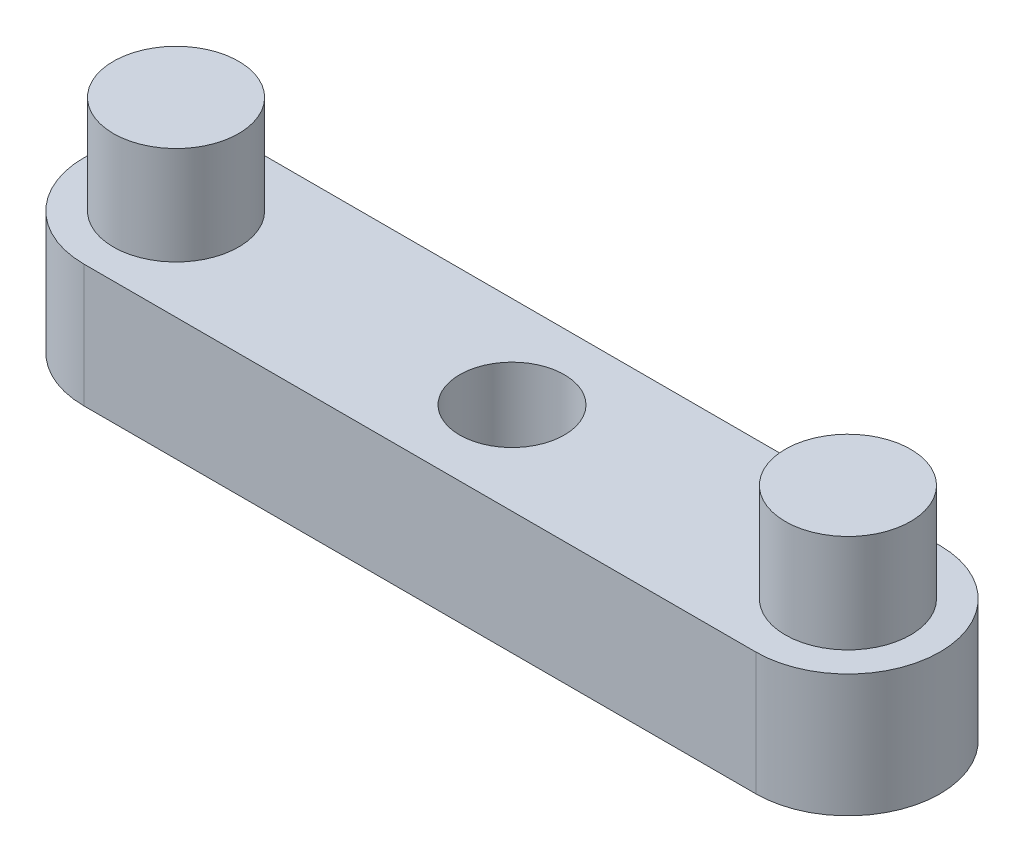
SolidWorks part; units mm, degrees
ref_plane "Front Plane" through (0, 0, 0) normal (0, 0, 1) x (1, 0, 0)
ref_plane "Top Plane" through (0, 0, 0) normal (0, 1, 0) x (1, 0, 0)
ref_plane "Right Plane" through (0, 0, 0) normal (1, 0, 0) x (0, 0, -1)
sketch "Sketch1" plane through (0, 0, 0) normal (0, 1, 0) x (1, 0, 0)
  line L0 (-13.675, 0) -> (13.675, 0) construction
  line L1 (-13.675, 3.75) -> (13.675, 3.75)
  line L2 (-13.675, -3.75) -> (13.675, -3.75)
  circle A0 centre (0, 0) radius 2.13
  arc A1 (-13.675, 3.75) -> (-13.675, -3.75) centre (-13.675, 0) ccw
  arc A2 (13.675, -3.75) -> (13.675, 3.75) centre (13.675, 0) ccw
  point P5 (0, 0)
  dimension "D1" = 4.26
  dimension "D2" = 7.5
  dimension "D3" = 27.35
extrude "Boss-Extrude1" add sketch "Sketch1" along normal blind 2.5 and the other way blind 2.5
sketch "Sketch2" plane through (0, 2.5, 0) normal (0, 1, 0) x (1, 0, 0)
  circle A0 centre (-13.675, 0) radius 2.55
  circle A1 centre (13.675, 0) radius 2.55
  point P4 (0, 0)
  point P6 (0, 0)
  dimension "D1" = 5.1
extrude "Boss-Extrude2" add sketch "Sketch2" along normal blind 4
